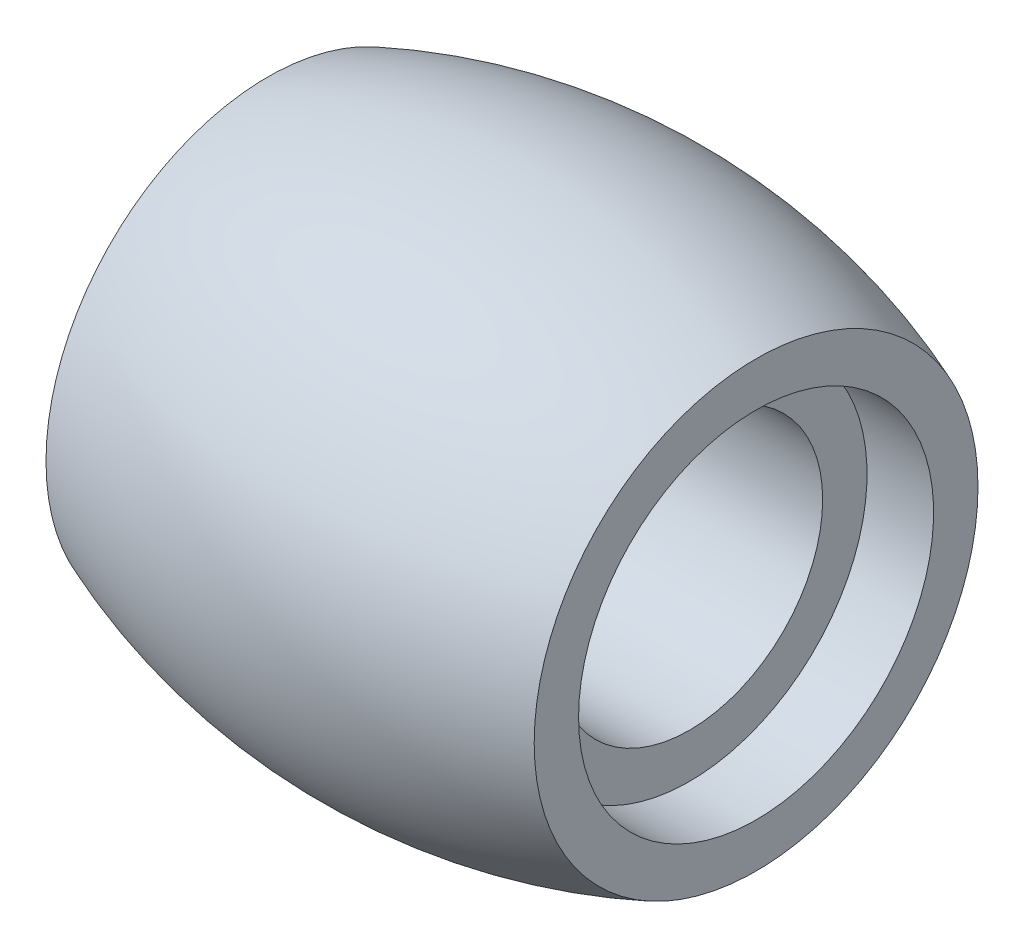
SolidWorks part; units mm, degrees
ref_plane "Front Plane" through (0, 0, 0) normal (0, 0, 1) x (1, 0, 0)
ref_plane "Top Plane" through (0, 0, 0) normal (0, 1, 0) x (1, 0, 0)
ref_plane "Right Plane" through (0, 0, 0) normal (1, 0, 0) x (0, 0, -1)
sketch "Sketch2" plane through (0, 0, 0) normal (0, 0, 1) x (1, 0, 0)
  line L0 (0, 6.5859) -> (0, -8.2148) construction
  line L1 (-8.918, 0) -> (11.5313, 0) construction
  line L2 (-4, 3) -> (4, 3)
  line L3 (4, 3) -> (4, 4)
  line L4 (4, 4) -> (5.5, 4)
  line L5 (5.5, 4) -> (5.5, 5)
  line L6 (-5.5, 4) -> (-5.5, 5)
  line L7 (-4, 4) -> (-5.5, 4)
  line L8 (-4, 3) -> (-4, 4)
  arc A0 (-5.5, 5) -> (5.5, 5) centre (0, -8.9553) cw
  point P18 (0, 3)
  dimension "D6" = 15
  dimension "1.5" = 3
  dimension "D2" = 1.5
  dimension "2.9" = 4
  dimension "D4" = 5
  dimension "D5" = 5.5
revolve "Revolve1" add sketch "Sketch2" angle 360 about L1
